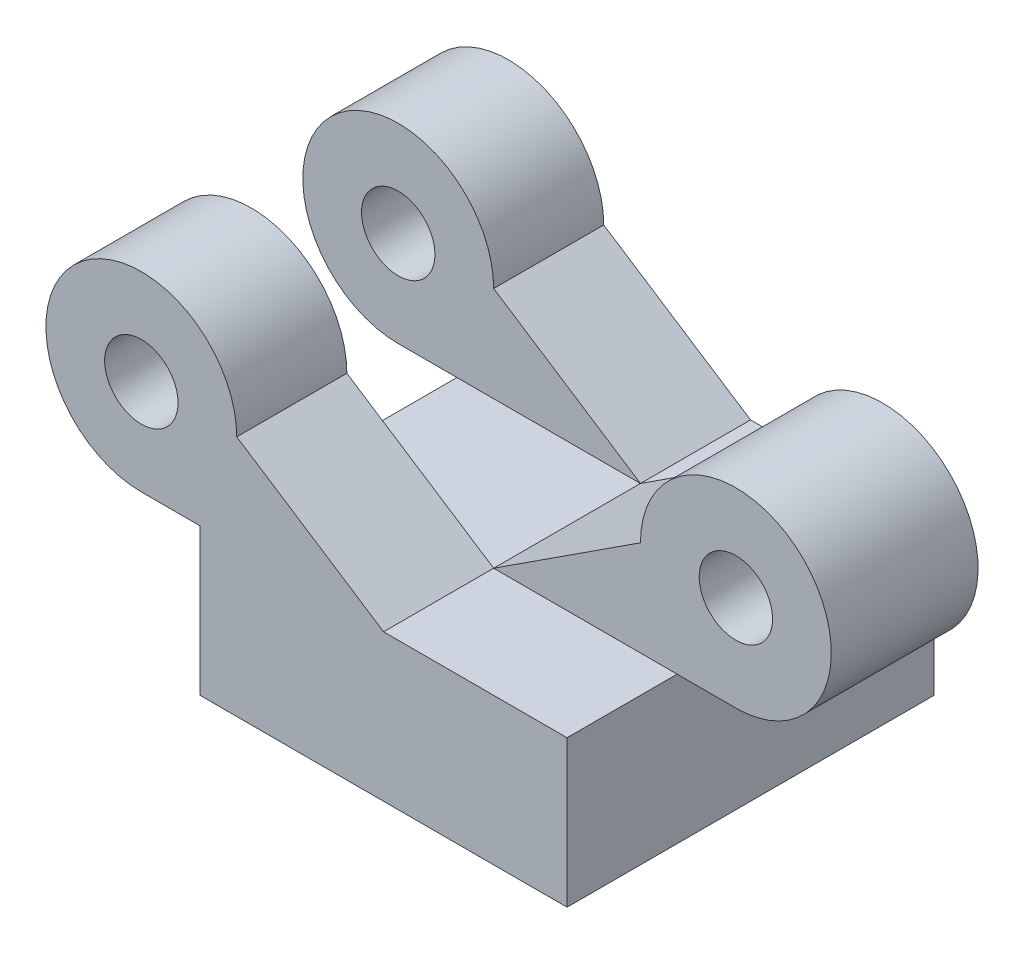
SolidWorks part; units mm, degrees
ref_plane "Front Plane" through (0, 0, 0) normal (0, 0, 1) x (1, 0, 0)
ref_plane "Top Plane" through (0, 0, 0) normal (0, 1, 0) x (1, 0, 0)
ref_plane "Right Plane" through (0, 0, 0) normal (1, 0, 0) x (0, 0, -1)
sketch "Sketch1" plane through (0, 0, 0) normal (0, 1, 0) x (1, 0, 0)
  line L1 (-12.5, 12.5) -> (12.5, 12.5)
  line L2 (-12.5, 12.5) -> (-12.5, -12.5)
  line L3 (-12.5, -12.5) -> (12.5, -12.5)
  line L4 (12.5, 12.5) -> (12.5, -12.5)
  line L5 (-12.5, 12.5) -> (12.5, -12.5) construction
  line L6 (-12.5, -12.5) -> (12.5, 12.5) construction
  point P0 (0, 0)
  dimension "D1" = 25
  dimension "D2" = 25
extrude "Boss-Extrude1" add sketch "Sketch1" against normal blind 10
sketch "Sketch2" plane through (0, 0, 0) normal (0, 0, 1) x (1, 0, 0)
  line L0 (-16.5, 6.5) -> (-16.5, 0) construction
  line L1 (-12.5, 0) -> (12.5, 0) construction
  line L2 (-16.5, 0) -> (-12.5, 0) construction
  line L3 (-12.5, 0) -> (-16.5, 6.5) construction
  line L4 (-16.5, 0) -> (-12.5, 0)
  line L5 (-10, 6.5) -> (0, 0)
  line L6 (-12.5, 0) -> (12.5, 0)
  line L7 (0, 0) -> (0, -10) construction
  line L8 (-12.5, -10) -> (12.5, -10) construction
  line L9 (10, 6.5) -> (0, 0)
  line L10 (16.5, 0) -> (12.5, 0)
  circle A0 centre (-16.5, 6.5) radius 6.5
  circle A1 centre (-16.5, 6.5) radius 2.5
  circle A2 centre (16.5, 6.5) radius 6.5
  circle A3 centre (16.5, 6.5) radius 2.5
  dimension "D1" = 4
  dimension "D2" = 5
  dimension "D3" = 4
extrude "Boss-Extrude2" add sketch "Sketch2" along normal blind 12.5 and the other way blind 12.5 contours A0 A1 | A0 L4 L6 L5 | L10 A2 L9 L6 | A2 A3 region at (-7.7105, 2.0108, 0) region at (7.7105, 2.0108, 0) region at (-20.9662, 10.9662, 0) region at (16.5, 12.8162, 0)
sketch "Sketch3" plane through (0, 0, 0) normal (0, 1, 0) x (1, 0, 0)
  line L0 (-23, 0) -> (23, 0) construction
  line L1 (-23, 12.5) -> (-23, -12.5) construction
  line L2 (23, -12.5) -> (23, 12.5) construction
  line L3 (0, -12.5) -> (0, 12.5) construction
  line L4 (0, 5) -> (-25.5198, 5)
  line L5 (0, 5) -> (0, -5)
  line L6 (0, -5) -> (-25.5198, -5)
  line L7 (-25.5198, 5) -> (-25.5198, -5)
  line L8 (-23, 0) -> (-25.5198, 0) construction
  line L10 (0, 5) -> (24.9004, 5)
  line L11 (0, 5) -> (0, 16.4246)
  line L12 (0, 16.4246) -> (24.9004, 16.4246)
  line L13 (24.9004, 5) -> (24.9004, 16.4246)
  line L14 (0, -5) -> (24.9004, -5)
  line L15 (0, -5) -> (0, -14.3859)
  line L16 (0, -14.3859) -> (24.9004, -14.3859)
  line L17 (24.9004, -5) -> (24.9004, -14.3859)
  dimension "D1" = 10
  dimension "D2" = 10
extrude "Cut-Extrude1" cut sketch "Sketch3" along normal blind 22.5 contours L4 L7 L6 L5 | L10 L13 L12 L11 | L17 L14 L15 L16 region at (-12.7599, 0, 0) region at (12.4502, 0, 9.6929) region at (12.4502, 0, -10.7123)
